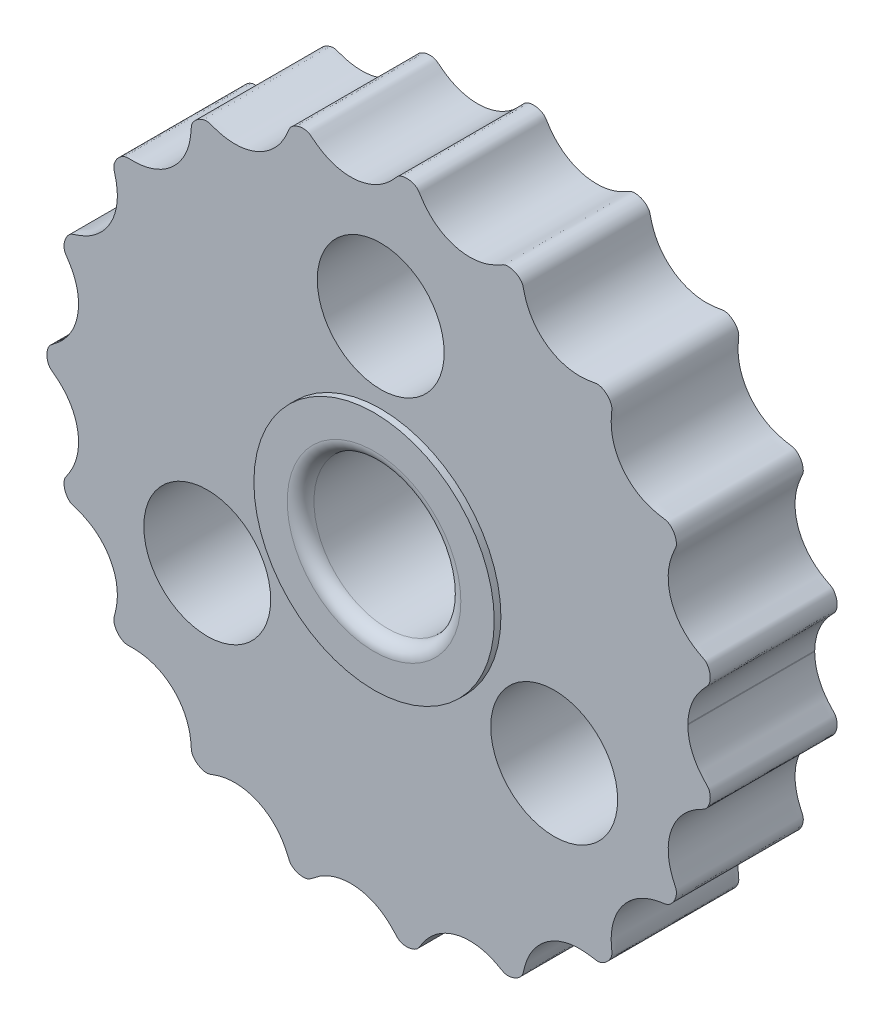
SolidWorks part; units mm, degrees
ref_plane "Ebene vorne" through (0, 0, 0) normal (0, 0, 1) x (1, 0, 0)
ref_plane "Ebene oben" through (0, 0, 0) normal (0, 1, 0) x (1, 0, 0)
ref_plane "Ebene rechts" through (0, 0, 0) normal (1, 0, 0) x (0, 0, -1)
sketch "Skizze1" plane through (0, 0, 0) normal (0, 0, 1) x (1, 0, 0)
  circle A0 centre (0, 0) radius 25
  dimension "D1" = 50
extrude "Aufsatz-Linear austragen1" add sketch "Skizze1" along normal blind 9.5 contours A0
sketch "Skizze3" plane through (0, 0, 9.5) normal (0, 0, 1) x (1, 0, 0)
  circle A0 centre (0, 25) radius 0.5
  circle A1 centre (0, 0) radius 25 construction
extrude "Schnitt-Linear austragen1" cut sketch "Skizze3" against normal up to next contours A0
pattern_circular "Kreismuster3" [suppressed] count 30 over 360 of bodies 102
sketch "Skizze9" plane through (0, 0, 9.5) normal (0, 0, 1) x (1, 0, 0)
  line L0 (23.0004, 0.0609) -> (23, 0)
  spline S0 degree 4 poles (21.8349, 10.4363) (21.7595, 10.2402) (21.6296, 9.8393) (21.51, 9.2154) (21.5169, 8.368) (21.6949, 7.529) (21.9996, 6.8362) (22.3616, 6.2918) (22.7278, 5.8789) (23.0126, 5.6175) (23.2743, 5.4145) (23.4929, 5.2661) (23.6607, 5.1622) (23.8217, 5.0701) (23.9556, 4.9977) (24.0711, 4.9376) (24.1728, 4.8842) (24.259, 4.8347) (24.3648, 4.7517) (24.4596, 4.6337) (24.5411, 4.4963) (24.6203, 4.3033) (24.6742, 4.0826) (24.6893, 3.8352) (24.654, 3.6047) (24.5939, 3.4337) (24.5231, 3.3149) (24.4482, 3.2274) (24.3391, 3.1139) (24.2149, 2.9815) (24.0838, 2.8346) (23.9185, 2.6346) (23.746, 2.4006) (23.5642, 2.1174) (23.3859, 1.7712) (23.2392, 1.419) (23.1381, 1.082) (23.0724, 0.8012) (23.0325, 0.5259) (23.0102, 0.3454) (22.9992, 0.0775) (22.999, -0.0665) (23.009, -0.3222) (23.0286, -0.4951) (23.0652, -0.7605) (23.1283, -1.0483) (23.2566, -1.484) (23.4559, -1.9318) (23.6809, -2.3132) (23.9099, -2.6224) (24.0743, -2.8241) (24.2067, -2.9723) (24.3336, -3.1084) (24.4467, -3.2256) (24.524, -3.3159) (24.583, -3.4156) (24.6246, -3.5208) (24.6638, -3.6686) (24.6852, -3.8609) (24.6735, -4.0869) (24.6205, -4.3068) (24.5464, -4.4848) (24.4695, -4.6144) (24.4037, -4.7024) (24.3311, -4.7784) (24.2516, -4.8395) (24.1377, -4.9039) (24.0001, -4.974) (23.846, -5.0565) (23.6352, -5.1762) (23.3933, -5.3292) (23.1212, -5.5276) (22.8316, -5.7799) (22.5655, -6.0569) (22.2617, -6.4361) (21.9548, -6.9332) (21.7249, -7.4811) (21.5829, -8.0653) (21.5273, -8.5636) (21.5216, -8.9708) (21.5541, -9.3694) (21.6218, -9.7561) (21.7087, -10.0818) (21.7995, -10.3483) (21.8842, -10.5632) (21.9558, -10.729) (22.0248, -10.8829) (22.0924, -11.0248) (22.1404, -11.1746) (22.1504, -11.3468) (22.1274, -11.5442) (22.061, -11.7619) (21.9505, -11.9788) (21.8083, -12.1674) (21.6614, -12.3022) (21.5247, -12.3914) (21.414, -12.4372) (21.3301, -12.4586) (21.2321, -12.4761) (21.1212, -12.4922) (20.9921, -12.5121) (20.8374, -12.539) (20.6763, -12.5709) (20.4655, -12.6198) (20.1205, -12.7175) (19.6539, -12.8972) (19.0899, -13.2109) (18.4957, -13.6939) (17.9798, -14.3033) (17.5818, -15.0184) (17.3599, -15.7125) (17.2758, -16.2728) (17.2579, -16.6757) (17.2603, -16.9123) (17.2683, -17.0871) (17.2802, -17.2498) (17.2921, -17.3816) (17.3037, -17.4944) (17.3123, -17.5952) (17.3148, -17.684) (17.3037, -17.7848) (17.2728, -17.8946) (17.2143, -18.0352) (17.1157, -18.1992) (16.9706, -18.3697) (16.7741, -18.5306) (16.5633, -18.6445) (16.3771, -18.7041) (16.228, -18.7183) (16.1024, -18.7064) (15.9827, -18.6847) (15.837, -18.6581) (15.664, -18.6292) (15.4825, -18.6042) (15.2505, -18.5802) (14.9676, -18.5655) (14.5429, -18.5729) (14.0693, -18.6361) (13.6043, -18.7559) (13.0666, -18.9667) (12.6278, -19.2052) (12.2149, -19.5036) (11.8389, -19.8586) (11.5583, -20.1838) (11.3157, -20.5303) (11.1115, -20.893) (10.9662, -21.2192) (10.865, -21.4994) (10.7941, -21.7329) (10.7511, -21.8937) (10.717, -22.0322) (10.6867, -22.159) (10.6596, -22.2741) (10.6135, -22.4098) (10.5273, -22.5357) (10.4274, -22.6442) (10.2911, -22.7583) (10.1265, -22.8625) (9.947, -22.94) (9.7581, -22.9885) (9.581, -23.009) (9.446, -23.0074) (9.3222, -22.9883) (9.215, -22.9494) (9.1367, -22.9105) (9.0374, -22.8556) (8.9163, -22.7867) (8.7704, -22.7082) (8.5994, -22.6214) (8.2969, -22.4821) (7.9364, -22.3488) (7.5146, -22.2402) (7.0313, -22.1759) (6.6328, -22.1607) (6.2298, -22.1836) (5.826, -22.2463) (5.4253, -22.3496) (5.032, -22.4941) (4.6565, -22.6767) (4.3023, -22.8948) (3.9755, -23.1429) (3.6777, -23.4168) (3.4441, -23.6748) (3.264, -23.904) (3.127, -24.0974) (3.026, -24.2496) (2.9434, -24.3794) (2.8771, -24.486) (2.8107, -24.5788) (2.7442, -24.6523) (2.6543, -24.7214) (2.5172, -24.8007) (2.3431, -24.8698) (2.129, -24.9172) (1.9104, -24.9257) (1.7254, -24.9049) (1.5597, -24.8634) (1.4272, -24.8123) (1.3018, -24.7374) (1.1919, -24.6254) (1.0929, -24.5126) (0.9862, -24.3949) (0.8714, -24.2728) (0.7167, -24.1173) (0.5166, -23.934) (0.1944, -23.6752) (-0.2816, -23.3734) (-0.8873, -23.1037) (-1.633, -22.9219) (-2.4119, -22.88) (-3.1838, -22.9833) (-3.829, -23.1953) (-4.2989, -23.431) (-4.6166, -23.6302) (-4.8236, -23.7746) (-4.9777, -23.8915) (-5.1193, -24.0037) (-5.2422, -24.1039) (-5.3368, -24.1704) (-5.4383, -24.2183) (-5.5428, -24.2496) (-5.6869, -24.2756) (-5.8715, -24.2822) (-6.0864, -24.2562) (-6.2931, -24.1927) (-6.4597, -24.1129) (-6.6006, -24.0204) (-6.7112, -23.9272) (-6.7966, -23.8241) (-6.8508, -23.7158) (-6.8984, -23.6058) (-6.9474, -23.4882) (-7.0086, -23.3469) (-7.0843, -23.183) (-7.1853, -22.982) (-7.3178, -22.7471) (-7.4915, -22.481) (-7.7159, -22.1922) (-7.9683, -21.919) (-8.2484, -21.6651) (-8.561, -21.4293) (-9, -21.1594) (-9.4852, -20.944) (-10.0058, -20.7949) (-10.5401, -20.7187) (-10.9664, -20.7017) (-11.386, -20.7263) (-11.7441, -20.7819) (-12.0407, -20.8508) (-12.2801, -20.9199) (-12.4645, -20.9804) (-12.619, -21.0347) (-12.7443, -21.0813) (-12.8432, -21.1127) (-12.9148, -21.1293) (-13.0155, -21.1409) (-13.1607, -21.1341) (-13.3458, -21.0947) (-13.5626, -21.0052) (-13.7727, -20.87) (-13.9463, -20.7079) (-14.067, -20.5439) (-14.1433, -20.3907) (-14.1772, -20.2506) (-14.1869, -20.1194) (-14.1984, -19.9464) (-14.2135, -19.7574) (-14.2357, -19.56) (-14.2744, -19.3096) (-14.3484, -18.9507) (-14.4988, -18.4602) (-14.7821, -17.8614) (-15.2347, -17.2299) (-15.8123, -16.6797) (-16.4915, -16.2457) (-17.1512, -15.9856) (-17.6884, -15.8653) (-18.0779, -15.8187) (-18.3444, -15.8008) (-18.5515, -15.7964) (-18.7472, -15.7971) (-18.9192, -15.8013) (-19.043, -15.798) (-19.1585, -15.7742) (-19.2639, -15.7342) (-19.3981, -15.6643) (-19.5524, -15.5524) (-19.7098, -15.3942) (-19.8355, -15.2104) (-19.9175, -15.0392) (-19.9694, -14.8748) (-19.9942, -14.7409) (-19.9941, -14.6091) (-19.9622, -14.4594) (-19.9209, -14.3132) (-19.8775, -14.147) (-19.8227, -13.9154) (-19.7703, -13.6388) (-19.7298, -13.3095) (-19.7155, -12.9316) (-19.7343, -12.5536) (-19.7865, -12.1771) (-19.8725, -11.8051) (-20.0235, -11.3478) (-20.2355, -10.9007) (-20.5061, -10.4779) (-20.8313, -10.0898) (-21.1296, -9.7984) (-21.4493, -9.5419) (-21.7859, -9.3207) (-22.0908, -9.1576) (-22.3541, -9.0395) (-22.5745, -8.9534) (-22.7489, -8.8919) (-22.9125, -8.8369) (-23.0664, -8.7897) (-23.2127, -8.7239) (-23.3488, -8.6133) (-23.48, -8.461) (-23.5959, -8.2631) (-23.6806, -8.0335) (-23.7223, -7.802) (-23.7216, -7.6015) (-23.6936, -7.4372) (-23.6459, -7.3113) (-23.587, -7.2131) (-23.5046, -7.0919) (-23.4135, -6.9559) (-23.317, -6.8055) (-23.1954, -6.601) (-23.0687, -6.3633) (-22.9383, -6.0757) (-22.7839, -5.6451) (-22.656, -5.1008) (-22.5992, -4.4221) (-22.6826, -3.6209) (-22.9272, -2.8308) (-23.2818, -2.1836) (-23.6363, -1.7308) (-23.9221, -1.4366) (-24.1011, -1.2722) (-24.239, -1.1546) (-24.372, -1.0482) (-24.4823, -0.963) (-24.578, -0.8915) (-24.662, -0.827) (-24.7323, -0.7672) (-24.8009, -0.6902) (-24.8613, -0.5932) (-24.925, -0.4573) (-24.9789, -0.2784) (-25.008, -0.0615) (-24.998, 0.1569) (-24.9616, 0.3399) (-24.9066, 0.5001) (-24.8504, 0.6156) (-24.7832, 0.7138) (-24.7061, 0.7903) (-24.6412, 0.8433) (-24.5549, 0.909) (-24.4487, 0.9887) (-24.3242, 1.0855) (-24.1833, 1.2011) (-24.0105, 1.3531) (-23.8111, 1.5469) (-23.5946, 1.788) (-23.3715, 2.0829) (-23.1734, 2.3976) (-23.0026, 2.7303) (-22.8251, 3.1685) (-22.6969, 3.6432) (-22.6277, 4.1442) (-22.6242, 4.6617) (-22.6664, 5.0951) (-22.7519, 5.5174) (-22.8777, 5.9244) (-23.0193, 6.2625) (-23.1587, 6.5356) (-23.2844, 6.7524) (-23.3883, 6.9169) (-23.4888, 7.0702) (-23.5875, 7.2108) (-23.6712, 7.3568) (-23.7142, 7.5309) (-23.7261, 7.7309) (-23.6995, 7.9535) (-23.6303, 8.1831) (-23.5263, 8.3908) (-23.4082, 8.549) (-23.2912, 8.6625) (-23.187, 8.7339) (-23.0968, 8.7758) (-22.9816, 8.8159) (-22.8484, 8.8583) (-22.6971, 8.9097) (-22.4871, 8.9859) (-22.2435, 9.0865) (-21.9662, 9.221) (-21.6596, 9.4005) (-21.366, 9.6063) (-21.0151, 9.8992) (-20.6164, 10.3191) (-20.2771, 10.8105) (-20.0144, 11.3636) (-19.8542, 11.8663) (-19.7673, 12.2789) (-19.7222, 12.6923) (-19.7169, 13.1024) (-19.7451, 13.4552) (-19.7902, 13.7494) (-19.8394, 13.9878) (-19.8839, 14.1718) (-19.9244, 14.3263) (-19.9596, 14.452) (-19.9815, 14.5509) (-19.9911, 14.6219) (-19.9935, 14.7217) (-19.9742, 14.8643) (-19.9195, 15.0445) (-19.8125, 15.2522) (-19.6794, 15.4254) (-19.5437, 15.5557) (-19.4017, 15.6607) (-19.2787, 15.7293) (-19.1504, 15.7794) (-19.0246, 15.7985) (-18.927, 15.8005) (-18.8133, 15.7991) (-18.6836, 15.7969) (-18.532, 15.7969) (-18.3106, 15.8023) (-18.0413, 15.8209) (-17.7248, 15.8628) (-17.3647, 15.941) (-16.9178, 16.0786) (-16.3974, 16.3085) (-15.8239, 16.6734) (-15.2485, 17.213) (-14.783, 17.8542) (-14.4878, 18.4827) (-14.3351, 18.9986) (-14.2627, 19.3751) (-14.2269, 19.6306) (-14.2075, 19.8274) (-14.1936, 20.0116) (-14.184, 20.1733) (-14.1697, 20.2905) (-14.1362, 20.4005) (-14.0873, 20.5015) (-14.0059, 20.6294) (-13.8804, 20.7742) (-13.7077, 20.9182) (-13.5127, 21.0276) (-13.335, 21.0939) (-13.1647, 21.1311) (-13.0232, 21.1444) (-12.8817, 21.1276) (-12.7469, 21.0817) (-12.6315, 21.0398) (-12.5001, 20.993) (-12.3519, 20.9431) (-12.1413, 20.8781) (-11.8655, 20.8075) (-11.5389, 20.7468) (-11.1616, 20.7097) (-10.7833, 20.7056) (-10.3038, 20.7432) (-9.7354, 20.8584) (-9.1818, 21.0633) (-8.6608, 21.3563) (-8.2599, 21.6542) (-7.9581, 21.9276) (-7.6875, 22.2243) (-7.4782, 22.5013) (-7.318, 22.7492) (-7.2006, 22.9556) (-7.1162, 23.1178) (-7.0401, 23.2775) (-6.9792, 23.4143) (-6.929, 23.5322) (-6.8829, 23.6417) (-6.8396, 23.7425) (-6.7732, 23.8583) (-6.6528, 23.9827) (-6.4911, 24.0996) (-6.2848, 24.1982) (-6.0489, 24.2635) (-5.8125, 24.2858) (-5.6133, 24.2679) (-5.4554, 24.2266) (-5.3475, 24.1752) (-5.2756, 24.1275) (-5.1963, 24.0667) (-5.1084, 23.9955) (-5.0052, 23.9133) (-4.8796, 23.817) (-4.7458, 23.7196) (-4.5657, 23.5973) (-4.2579, 23.4095) (-3.8065, 23.1883) (-3.1897, 22.9875) (-2.4297, 22.8812) (-1.6328, 22.9188) (-0.8411, 23.1135) (-0.1854, 23.421) (0.2799, 23.7378) (0.5861, 23.9964) (0.7572, 24.1576) (0.8795, 24.2813) (0.9904, 24.3996) (1.0788, 24.4971) (1.1534, 24.5815) (1.2215, 24.6556) (1.2849, 24.7171) (1.366, 24.7765) (1.4665, 24.8274) (1.6073, 24.879) (1.7912, 24.9173) (2.0109, 24.9275) (2.2284, 24.8982) (2.4076, 24.8457) (2.5635, 24.7759) (2.6787, 24.7064) (2.7776, 24.6216) (2.853, 24.522) (2.9089, 24.4353) (2.9741, 24.3312) (3.0513, 24.2111) (3.1673, 24.0378) (3.3314, 23.8136) (3.5412, 23.5623) (3.803, 23.2967) (4.0867, 23.0548) (4.3911, 22.8375) (4.7145, 22.6472) (5.1434, 22.4443) (5.6099, 22.2897) (6.1032, 22.1928) (6.6136, 22.1597) (7.04, 22.1755) (7.456, 22.233) (7.8578, 22.329) (8.1935, 22.443) (8.4659, 22.558) (8.6842, 22.6634) (8.8514, 22.7516) (9.0063, 22.8365) (9.1484, 22.9196) (9.3008, 22.9869) (9.4518, 23.0083) (9.5997, 23.0081) (9.7768, 22.9846) (9.9657, 22.9334) (10.1449, 22.8528) (10.3091, 22.7455) (10.4441, 22.6278) (10.5341, 22.5264) (10.6032, 22.4212) (10.6459, 22.3149) (10.6698, 22.2304) (10.6965, 22.1196) (10.7284, 21.9833) (10.7696, 21.8219) (10.8224, 21.6365) (10.926, 21.3181) (11.074, 20.9612) (11.2824, 20.576) (11.5658, 20.1761) (11.8273, 19.8724) (12.1194, 19.5924) (12.4404, 19.3397) (12.8767, 19.0608) (13.3474, 18.8414) (13.8414, 18.6865) (14.3466, 18.5977) (14.6978, 18.5693) (14.9983, 18.5678) (15.2424, 18.5806) (15.4319, 18.5983) (15.6163, 18.622) (15.7956, 18.651) (15.9629, 18.6804) (16.1188, 18.7114) (16.2634, 18.7186) (16.3919, 18.6957) (16.5434, 18.6484) (16.7128, 18.5663) (16.8932, 18.44) (17.0477, 18.2836) (17.1576, 18.1324) (17.2387, 17.9815) (17.2904, 17.8485) (17.3189, 17.7045) (17.3093, 17.5471) (17.2934, 17.3968) (17.2791, 17.2377) (17.2672, 17.07) (17.2581, 16.8499) (17.2594, 16.5774) (17.2886, 16.1632) (17.3914, 15.6061) (17.6071, 14.9758) (17.9828, 14.3047) (18.4824, 13.7066) (19.0811, 13.2137) (19.6713, 12.887) (20.16, 12.7034) (20.5195, 12.6059) (20.7644, 12.5521) (20.9536, 12.5182) (21.1309, 12.4903) (21.2868, 12.4679) (21.399, 12.4432) (21.5025, 12.4008) (21.5963, 12.345) (21.7134, 12.2561) (21.8437, 12.1238) (21.9702, 11.9469) (22.0634, 11.7504) (22.117, 11.5726) (22.1436, 11.4054) (22.149, 11.2598) (22.129, 11.1267) (22.0845, 11.0132) (22.035, 10.903) (21.9816, 10.7867) (21.919, 10.6454) (21.8499, 10.4782) (21.7706, 10.2666) (21.6878, 10.0086) (21.6103, 9.6986) (21.5509, 9.3355) (21.5224, 8.9626) (21.5272, 8.5827) (21.5787, 8.0866) (21.6972, 7.5846) (21.8865, 7.0905) (22.1457, 6.6199) (22.3909, 6.2662) (22.6666, 5.9438) (22.9679, 5.6541) (23.2503, 5.43) (23.5008, 5.2597) (23.7129, 5.1314) (23.8814, 5.0373) (24.0251, 4.9609) (24.1437, 4.9005) (24.2332, 4.8492) (24.2935, 4.8079) (24.37, 4.7415) (24.4633, 4.6297) (24.5599, 4.466) (24.6407, 4.2447) (24.683, 3.9972) (24.6804, 3.7586) (24.6403, 3.558) (24.5776, 3.3979) (24.4956, 3.2786) (24.4048, 3.1827) (24.2851, 3.0565) (24.1558, 2.9165) (24.0253, 2.7659) (23.8669, 2.5657) (23.6527, 2.2673) (23.442, 1.9019) (23.2546, 1.4742) (23.132, 1.0608) (23.0706, 0.7861) (23.0335, 0.5349) (23.0132, 0.3678) (23.0003, 0.1223) (22.9986, -0.0189) (23.0056, -0.2852) (23.0253, -0.4661) (23.0615, -0.7427) (23.1239, -1.029) (23.2494, -1.4644) (23.4447, -1.9094) (23.6681, -2.2941) (23.8991, -2.6086) (24.0657, -2.8141) (24.1984, -2.9632) (24.3246, -3.0987) (24.4356, -3.2143) (24.5132, -3.3018) (24.5877, -3.4196) (24.6374, -3.5547) (24.6701, -3.7073) (24.6838, -3.9154) (24.6644, -4.1417) (24.6, -4.381) (24.4916, -4.5912) (24.3759, -4.7394) (24.2736, -4.8247) (24.1898, -4.8749) (24.0901, -4.9279) (23.9765, -4.9865) (23.845, -5.0574) (23.6862, -5.1471) (23.5208, -5.2483) (23.3047, -5.3926) (23.0455, -5.59) (22.7627, -5.8442) (22.3976, -6.2458) (22.0314, -6.7792) (21.7172, -7.4627) (21.5252, -8.2962) (21.504, -9.1452) (21.6139, -9.7724) (21.7382, -10.176) (21.8113, -10.3736) knots 0 0 0 0 0 0.004237 0.008483 0.012729 0.016973 0.021413 0.023634 0.025855 0.02808 0.029193 0.030306 0.031182 0.032058 0.032934 0.033372 0.03381 0.034372 0.034934 0.036073 0.036831 0.037589 0.039124 0.04064 0.041779 0.042264 0.042749 0.043421 0.044093 0.045438 0.046411 0.047385 0.049332 0.051278 0.053223 0.055168 0.057112 0.0582 0.059287 0.060374 0.061462 0.062481 0.063501 0.064521 0.06554 0.067576 0.069612 0.073551 0.075471 0.07643 0.07739 0.078785 0.079482 0.08018 0.080676 0.081172 0.081811 0.082451 0.083753 0.085056 0.086348 0.086986 0.087623 0.08809 0.088558 0.089098 0.089639 0.090721 0.091672 0.092623 0.094526 0.09649 0.098454 0.100357 0.102259 0.106274 0.110193 0.112266 0.114339 0.116366 0.118392 0.120318 0.122244 0.123155 0.124065 0.124975 0.125886 0.126558 0.12723 0.128129 0.12933 0.130553 0.131784 0.13302 0.134061 0.134556 0.135052 0.135429 0.135805 0.136559 0.137312 0.138066 0.138968 0.13987 0.141675 0.145292 0.149024 0.152819 0.157032 0.161293 0.165414 0.167417 0.168419 0.16942 0.170182 0.170945 0.171707 0.172088 0.17247 0.172983 0.173496 0.174127 0.174758 0.176047 0.177335 0.178622 0.179842 0.180858 0.181239 0.181621 0.182383 0.183306 0.18423 0.185154 0.186077 0.188008 0.189939 0.193707 0.195683 0.19766 0.201566 0.203743 0.205919 0.208066 0.210213 0.212256 0.214298 0.215257 0.216216 0.217175 0.217654 0.218133 0.218845 0.219557 0.220527 0.221173 0.221818 0.22313 0.224442 0.22509 0.225738 0.226717 0.227156 0.227596 0.228035 0.228475 0.229441 0.230408 0.231375 0.232341 0.236155 0.238143 0.24013 0.242157 0.244184 0.24627 0.248355 0.250487 0.252618 0.254674 0.25673 0.258747 0.260763 0.261683 0.262604 0.263524 0.264444 0.264789 0.265133 0.265821 0.26644 0.267059 0.26832 0.269582 0.270836 0.271447 0.272058 0.273021 0.273691 0.274361 0.275205 0.27605 0.276894 0.277739 0.279628 0.281518 0.285219 0.28907 0.292926 0.296908 0.300855 0.304679 0.306545 0.307478 0.308411 0.309767 0.310445 0.311123 0.311607 0.31209 0.312702 0.313313 0.314555 0.3158 0.31704 0.317653 0.318265 0.319194 0.319946 0.320323 0.320699 0.321608 0.322518 0.323427 0.324337 0.326144 0.327952 0.329828 0.331704 0.333634 0.335564 0.337712 0.342077 0.344294 0.346435 0.348576 0.350665 0.352755 0.353733 0.35471 0.355688 0.356666 0.357036 0.357406 0.357777 0.358147 0.359078 0.360318 0.361577 0.362842 0.364095 0.365072 0.365667 0.366263 0.366989 0.367716 0.369169 0.370082 0.370996 0.372823 0.376553 0.380398 0.384283 0.388402 0.39254 0.396544 0.398494 0.399468 0.400443 0.401928 0.402671 0.403414 0.403914 0.404414 0.405044 0.405674 0.406958 0.408242 0.409517 0.410142 0.410767 0.411715 0.412247 0.41278 0.413844 0.414778 0.415711 0.417578 0.419518 0.421458 0.423328 0.425198 0.427172 0.429146 0.433023 0.435141 0.437259 0.439338 0.441417 0.443393 0.445369 0.446301 0.447232 0.448164 0.449096 0.449784 0.450473 0.451382 0.452594 0.453825 0.455064 0.456299 0.457303 0.457852 0.458401 0.459003 0.459604 0.460806 0.461705 0.462604 0.464401 0.466234 0.468066 0.471816 0.475642 0.479892 0.484207 0.488376 0.490424 0.491448 0.492472 0.493275 0.494078 0.494881 0.495283 0.495684 0.496212 0.496739 0.497357 0.497975 0.499232 0.500491 0.501743 0.502362 0.50298 0.503902 0.504323 0.504745 0.505167 0.505588 0.506507 0.507426 0.508345 0.509264 0.511146 0.513029 0.51487 0.51671 0.518635 0.520559 0.52439 0.526593 0.528795 0.530975 0.533155 0.535264 0.537372 0.538353 0.539334 0.540315 0.541296 0.542048 0.5428 0.543686 0.54487 0.546076 0.547289 0.548505 0.549524 0.55004 0.550557 0.551041 0.551525 0.552494 0.553378 0.554262 0.556029 0.557808 0.559586 0.561418 0.563249 0.567013 0.571226 0.573386 0.575547 0.57763 0.579713 0.581758 0.583803 0.584757 0.585711 0.586665 0.587619 0.587981 0.588342 0.588703 0.589064 0.589991 0.591226 0.592482 0.593745 0.594375 0.595005 0.596035 0.596581 0.597126 0.597563 0.597999 0.598872 0.599744 0.600617 0.602465 0.604312 0.606175 0.608037 0.611883 0.615748 0.619804 0.623847 0.62776 0.629667 0.63062 0.631574 0.63296 0.633653 0.634347 0.63484 0.635333 0.635965 0.636598 0.63789 0.639181 0.640471 0.641084 0.641696 0.642695 0.643315 0.643934 0.644554 0.645174 0.64613 0.647085 0.648997 0.65091 0.652822 0.654719 0.656616 0.660595 0.664476 0.666551 0.668626 0.67065 0.672674 0.674636 0.675617 0.676598 0.67746 0.678322 0.679184 0.679615 0.680046 0.680718 0.68139 0.682294 0.683501 0.68473 0.685967 0.68721 0.688256 0.688745 0.689234 0.689614 0.689994 0.690755 0.691516 0.692276 0.693184 0.694091 0.695906 0.699541 0.703294 0.707104 0.711296 0.715529 0.719623 0.721614 0.722609 0.723605 0.724363 0.72512 0.725878 0.726257 0.726636 0.727147 0.727657 0.728278 0.728898 0.730163 0.731429 0.732687 0.7333 0.733914 0.734868 0.735387 0.735906 0.736425 0.736945 0.737866 0.738787 0.740628 0.742544 0.74446 0.746298 0.748136 0.750076 0.752015 0.75585 0.758014 0.760177 0.762308 0.764439 0.766466 0.768494 0.769446 0.770399 0.771352 0.772304 0.773011 0.773717 0.774692 0.775341 0.77599 0.777308 0.778627 0.779278 0.77993 0.780912 0.781353 0.781795 0.782237 0.782678 0.78365 0.784622 0.785593 0.786565 0.790399 0.792398 0.794396 0.796432 0.798468 0.800544 0.802619 0.806855 0.808898 0.810941 0.812947 0.81395 0.814953 0.815868 0.816783 0.817698 0.818613 0.819297 0.819981 0.820603 0.821225 0.822492 0.82376 0.825019 0.825633 0.826247 0.827208 0.827886 0.828563 0.829411 0.830258 0.831106 0.831953 0.833852 0.83575 0.83947 0.843342 0.847212 0.851172 0.85509 0.858888 0.860742 0.861669 0.862595 0.863943 0.864616 0.86529 0.86577 0.866251 0.866866 0.86748 0.868728 0.86998 0.871226 0.871843 0.872459 0.87339 0.87415 0.87453 0.874909 0.875821 0.876733 0.877645 0.878557 0.880376 0.882194 0.884081 0.885968 0.887906 0.889845 0.894123 0.896327 0.898531 0.900659 0.902786 0.904866 0.906945 0.907918 0.90889 0.909862 0.910835 0.911203 0.911571 0.911939 0.912307 0.913243 0.914489 0.915755 0.917025 0.918283 0.919266 0.919863 0.920461 0.92119 0.921919 0.923377 0.924296 0.925215 0.927054 0.930802 0.932735 0.934668 0.935643 0.936618 0.937593 0.938568 0.939657 0.940745 0.941834 0.942922 0.944896 0.946869 0.950817 0.952789 0.953776 0.954762 0.956135 0.956821 0.957507 0.957996 0.958485 0.959623 0.960381 0.961139 0.962673 0.964189 0.965328 0.965881 0.966433 0.966863 0.967294 0.968154 0.969015 0.969875 0.970969 0.972064 0.974253 0.976438 0.978623 0.98299 0.987244 0.991499 0.995751 1 1 1 1 1 construction
  spline S1 degree 4 poles (23, 0) (23, -0.0443) (23.0016, -0.1335) (23.009, -0.3222) (23.0286, -0.4951) (23.0652, -0.7605) (23.1283, -1.0483) (23.2566, -1.484) (23.4559, -1.9318) (23.6809, -2.3132) (23.9099, -2.6224) (24.0743, -2.8241) (24.2067, -2.9723) (24.3336, -3.1084) (24.4467, -3.2256) (24.524, -3.3159) (24.583, -3.4156) (24.6246, -3.5208) (24.6638, -3.6686) (24.6852, -3.8609) (24.6735, -4.0869) (24.6205, -4.3068) (24.5464, -4.4848) (24.4695, -4.6144) (24.4037, -4.7024) (24.3311, -4.7784) (24.2516, -4.8395) (24.1377, -4.9039) (24.0001, -4.974) (23.846, -5.0565) (23.6352, -5.1762) (23.3933, -5.3292) (23.1212, -5.5276) (22.8316, -5.7799) (22.5655, -6.0569) (22.2617, -6.4361) (21.9548, -6.9332) (21.7249, -7.4811) (21.5829, -8.0653) (21.5273, -8.5636) (21.5216, -8.9708) (21.5541, -9.3694) (21.6218, -9.7561) (21.7087, -10.0818) (21.7995, -10.3483) (21.8842, -10.5632) (21.9558, -10.729) (22.0248, -10.8829) (22.0924, -11.0248) (22.1404, -11.1746) (22.1504, -11.3468) (22.1274, -11.5442) (22.061, -11.7619) (21.9505, -11.9788) (21.8083, -12.1674) (21.6614, -12.3022) (21.5247, -12.3914) (21.414, -12.4372) (21.3301, -12.4586) (21.2321, -12.4761) (21.1212, -12.4922) (20.9921, -12.5121) (20.8374, -12.539) (20.6763, -12.5709) (20.4655, -12.6198) (20.1205, -12.7175) (19.6539, -12.8972) (19.0899, -13.2109) (18.4957, -13.6939) (17.9798, -14.3033) (17.5818, -15.0184) (17.3599, -15.7125) (17.2758, -16.2728) (17.2579, -16.6757) (17.2603, -16.9123) (17.2683, -17.0871) (17.2802, -17.2498) (17.2921, -17.3816) (17.3037, -17.4944) (17.3123, -17.5952) (17.3148, -17.684) (17.3037, -17.7848) (17.2728, -17.8946) (17.2143, -18.0352) (17.1157, -18.1992) (16.9706, -18.3697) (16.7741, -18.5306) (16.5633, -18.6445) (16.3771, -18.7041) (16.228, -18.7183) (16.1024, -18.7064) (15.9827, -18.6847) (15.837, -18.6581) (15.664, -18.6292) (15.4825, -18.6042) (15.2505, -18.5802) (14.9676, -18.5655) (14.5429, -18.5729) (14.0693, -18.6361) (13.6043, -18.7559) (13.0666, -18.9667) (12.6278, -19.2052) (12.2149, -19.5036) (11.8389, -19.8586) (11.5583, -20.1838) (11.3157, -20.5303) (11.1115, -20.893) (10.9662, -21.2192) (10.865, -21.4994) (10.7941, -21.7329) (10.7511, -21.8937) (10.717, -22.0322) (10.6867, -22.159) (10.6596, -22.2741) (10.6135, -22.4098) (10.5273, -22.5357) (10.4274, -22.6442) (10.2911, -22.7583) (10.1265, -22.8625) (9.947, -22.94) (9.7581, -22.9885) (9.581, -23.009) (9.446, -23.0074) (9.3222, -22.9883) (9.215, -22.9494) (9.1367, -22.9105) (9.0374, -22.8556) (8.9163, -22.7867) (8.7704, -22.7082) (8.5994, -22.6214) (8.2969, -22.4821) (7.9364, -22.3488) (7.5146, -22.2402) (7.0313, -22.1759) (6.6328, -22.1607) (6.2298, -22.1836) (5.826, -22.2463) (5.4253, -22.3496) (5.032, -22.4941) (4.6565, -22.6767) (4.3023, -22.8948) (3.9755, -23.1429) (3.6777, -23.4168) (3.4441, -23.6748) (3.264, -23.904) (3.127, -24.0974) (3.026, -24.2496) (2.9434, -24.3794) (2.8771, -24.486) (2.8107, -24.5788) (2.7442, -24.6523) (2.6543, -24.7214) (2.5172, -24.8007) (2.3431, -24.8698) (2.129, -24.9172) (1.9104, -24.9257) (1.7254, -24.9049) (1.5597, -24.8634) (1.4272, -24.8123) (1.3018, -24.7374) (1.1919, -24.6254) (1.0929, -24.5126) (0.9862, -24.3949) (0.8714, -24.2728) (0.7167, -24.1173) (0.5166, -23.934) (0.1944, -23.6752) (-0.2816, -23.3734) (-0.8873, -23.1037) (-1.633, -22.9219) (-2.4119, -22.88) (-3.1838, -22.9833) (-3.829, -23.1953) (-4.2989, -23.431) (-4.6166, -23.6302) (-4.8236, -23.7746) (-4.9777, -23.8915) (-5.1193, -24.0037) (-5.2422, -24.1039) (-5.3368, -24.1704) (-5.4383, -24.2183) (-5.5428, -24.2496) (-5.6869, -24.2756) (-5.8715, -24.2822) (-6.0864, -24.2562) (-6.2931, -24.1927) (-6.4597, -24.1129) (-6.6006, -24.0204) (-6.7112, -23.9272) (-6.7966, -23.8241) (-6.8508, -23.7158) (-6.8984, -23.6058) (-6.9474, -23.4882) (-7.0086, -23.3469) (-7.0843, -23.183) (-7.1853, -22.982) (-7.3178, -22.7471) (-7.4915, -22.481) (-7.7159, -22.1922) (-7.9683, -21.919) (-8.2484, -21.6651) (-8.561, -21.4293) (-9, -21.1594) (-9.4852, -20.944) (-10.0058, -20.7949) (-10.5401, -20.7187) (-10.9664, -20.7017) (-11.386, -20.7263) (-11.7441, -20.7819) (-12.0407, -20.8508) (-12.2801, -20.9199) (-12.4645, -20.9804) (-12.619, -21.0347) (-12.7443, -21.0813) (-12.8432, -21.1127) (-12.9148, -21.1293) (-13.0155, -21.1409) (-13.1607, -21.1341) (-13.3458, -21.0947) (-13.5626, -21.0052) (-13.7727, -20.87) (-13.9463, -20.7079) (-14.067, -20.5439) (-14.1433, -20.3907) (-14.1772, -20.2506) (-14.1869, -20.1194) (-14.1984, -19.9464) (-14.2135, -19.7574) (-14.2357, -19.56) (-14.2744, -19.3096) (-14.3484, -18.9507) (-14.4988, -18.4602) (-14.7821, -17.8614) (-15.2347, -17.2299) (-15.8123, -16.6797) (-16.4915, -16.2457) (-17.1512, -15.9856) (-17.6884, -15.8653) (-18.0779, -15.8187) (-18.3444, -15.8008) (-18.5515, -15.7964) (-18.7472, -15.7971) (-18.9192, -15.8013) (-19.043, -15.798) (-19.1585, -15.7742) (-19.2639, -15.7342) (-19.3981, -15.6643) (-19.5524, -15.5524) (-19.7098, -15.3942) (-19.8355, -15.2104) (-19.9175, -15.0392) (-19.9694, -14.8748) (-19.9942, -14.7409) (-19.9941, -14.6091) (-19.9622, -14.4594) (-19.9209, -14.3132) (-19.8775, -14.147) (-19.8227, -13.9154) (-19.7703, -13.6388) (-19.7298, -13.3095) (-19.7155, -12.9316) (-19.7343, -12.5536) (-19.7865, -12.1771) (-19.8725, -11.8051) (-20.0235, -11.3478) (-20.2355, -10.9007) (-20.5061, -10.4779) (-20.8313, -10.0898) (-21.1296, -9.7984) (-21.4493, -9.5419) (-21.7859, -9.3207) (-22.0908, -9.1576) (-22.3541, -9.0395) (-22.5745, -8.9534) (-22.7489, -8.8919) (-22.9125, -8.8369) (-23.0664, -8.7897) (-23.2127, -8.7239) (-23.3488, -8.6133) (-23.48, -8.461) (-23.5959, -8.2631) (-23.6806, -8.0335) (-23.7223, -7.802) (-23.7216, -7.6015) (-23.6936, -7.4372) (-23.6459, -7.3113) (-23.587, -7.2131) (-23.5046, -7.0919) (-23.4135, -6.9559) (-23.317, -6.8055) (-23.1954, -6.601) (-23.0687, -6.3633) (-22.9383, -6.0757) (-22.7839, -5.6451) (-22.656, -5.1008) (-22.5992, -4.4221) (-22.6826, -3.6209) (-22.9272, -2.8308) (-23.2818, -2.1836) (-23.6363, -1.7308) (-23.9221, -1.4366) (-24.1011, -1.2722) (-24.239, -1.1546) (-24.372, -1.0482) (-24.4823, -0.963) (-24.578, -0.8915) (-24.662, -0.827) (-24.7323, -0.7672) (-24.8009, -0.6902) (-24.8613, -0.5932) (-24.925, -0.4573) (-24.9789, -0.2784) (-25.008, -0.0615) (-24.998, 0.1569) (-24.9616, 0.3399) (-24.9066, 0.5001) (-24.8504, 0.6156) (-24.7832, 0.7138) (-24.7061, 0.7903) (-24.6412, 0.8433) (-24.5549, 0.909) (-24.4487, 0.9887) (-24.3242, 1.0855) (-24.1833, 1.2011) (-24.0105, 1.3531) (-23.8111, 1.5469) (-23.5946, 1.788) (-23.3715, 2.0829) (-23.1734, 2.3976) (-23.0026, 2.7303) (-22.8251, 3.1685) (-22.6969, 3.6432) (-22.6277, 4.1442) (-22.6242, 4.6617) (-22.6664, 5.0951) (-22.7519, 5.5174) (-22.8777, 5.9244) (-23.0193, 6.2625) (-23.1587, 6.5356) (-23.2844, 6.7524) (-23.3883, 6.9169) (-23.4888, 7.0702) (-23.5875, 7.2108) (-23.6712, 7.3568) (-23.7142, 7.5309) (-23.7261, 7.7309) (-23.6995, 7.9535) (-23.6303, 8.1831) (-23.5263, 8.3908) (-23.4082, 8.549) (-23.2912, 8.6625) (-23.187, 8.7339) (-23.0968, 8.7758) (-22.9816, 8.8159) (-22.8484, 8.8583) (-22.6971, 8.9097) (-22.4871, 8.9859) (-22.2435, 9.0865) (-21.9662, 9.221) (-21.6596, 9.4005) (-21.366, 9.6063) (-21.0151, 9.8992) (-20.6164, 10.3191) (-20.2771, 10.8105) (-20.0144, 11.3636) (-19.8542, 11.8663) (-19.7673, 12.2789) (-19.7222, 12.6923) (-19.7169, 13.1024) (-19.7451, 13.4552) (-19.7902, 13.7494) (-19.8394, 13.9878) (-19.8839, 14.1718) (-19.9244, 14.3263) (-19.9596, 14.452) (-19.9815, 14.5509) (-19.9911, 14.6219) (-19.9935, 14.7217) (-19.9742, 14.8643) (-19.9195, 15.0445) (-19.8125, 15.2522) (-19.6794, 15.4254) (-19.5437, 15.5557) (-19.4017, 15.6607) (-19.2787, 15.7293) (-19.1504, 15.7794) (-19.0246, 15.7985) (-18.927, 15.8005) (-18.8133, 15.7991) (-18.6836, 15.7969) (-18.532, 15.7969) (-18.3106, 15.8023) (-18.0413, 15.8209) (-17.7248, 15.8628) (-17.3647, 15.941) (-16.9178, 16.0786) (-16.3974, 16.3085) (-15.8239, 16.6734) (-15.2485, 17.213) (-14.783, 17.8542) (-14.4878, 18.4827) (-14.3351, 18.9986) (-14.2627, 19.3751) (-14.2269, 19.6306) (-14.2075, 19.8274) (-14.1936, 20.0116) (-14.184, 20.1733) (-14.1697, 20.2905) (-14.1362, 20.4005) (-14.0873, 20.5015) (-14.0059, 20.6294) (-13.8804, 20.7742) (-13.7077, 20.9182) (-13.5127, 21.0276) (-13.335, 21.0939) (-13.1647, 21.1311) (-13.0232, 21.1444) (-12.8817, 21.1276) (-12.7469, 21.0817) (-12.6315, 21.0398) (-12.5001, 20.993) (-12.3519, 20.9431) (-12.1413, 20.8781) (-11.8655, 20.8075) (-11.5389, 20.7468) (-11.1616, 20.7097) (-10.7833, 20.7056) (-10.3038, 20.7432) (-9.7354, 20.8584) (-9.1818, 21.0633) (-8.6608, 21.3563) (-8.2599, 21.6542) (-7.9581, 21.9276) (-7.6875, 22.2243) (-7.4782, 22.5013) (-7.318, 22.7492) (-7.2006, 22.9556) (-7.1162, 23.1178) (-7.0401, 23.2775) (-6.9792, 23.4143) (-6.929, 23.5322) (-6.8829, 23.6417) (-6.8396, 23.7425) (-6.7732, 23.8583) (-6.6528, 23.9827) (-6.4911, 24.0996) (-6.2848, 24.1982) (-6.0489, 24.2635) (-5.8125, 24.2858) (-5.6133, 24.2679) (-5.4554, 24.2266) (-5.3475, 24.1752) (-5.2756, 24.1275) (-5.1963, 24.0667) (-5.1084, 23.9955) (-5.0052, 23.9133) (-4.8796, 23.817) (-4.7458, 23.7196) (-4.5657, 23.5973) (-4.2579, 23.4095) (-3.8065, 23.1883) (-3.1897, 22.9875) (-2.4297, 22.8812) (-1.6328, 22.9188) (-0.8411, 23.1135) (-0.1854, 23.421) (0.2799, 23.7378) (0.5861, 23.9964) (0.7572, 24.1576) (0.8795, 24.2813) (0.9904, 24.3996) (1.0788, 24.4971) (1.1534, 24.5815) (1.2215, 24.6556) (1.2849, 24.7171) (1.366, 24.7765) (1.4665, 24.8274) (1.6073, 24.879) (1.7912, 24.9173) (2.0109, 24.9275) (2.2284, 24.8982) (2.4076, 24.8457) (2.5635, 24.7759) (2.6787, 24.7064) (2.7776, 24.6216) (2.853, 24.522) (2.9089, 24.4353) (2.9741, 24.3312) (3.0513, 24.2111) (3.1673, 24.0378) (3.3314, 23.8136) (3.5412, 23.5623) (3.803, 23.2967) (4.0867, 23.0548) (4.3911, 22.8375) (4.7145, 22.6472) (5.1434, 22.4443) (5.6099, 22.2897) (6.1032, 22.1928) (6.6136, 22.1597) (7.04, 22.1755) (7.456, 22.233) (7.8578, 22.329) (8.1935, 22.443) (8.4659, 22.558) (8.6842, 22.6634) (8.8514, 22.7516) (9.0063, 22.8365) (9.1484, 22.9196) (9.3008, 22.9869) (9.4518, 23.0083) (9.5997, 23.0081) (9.7768, 22.9846) (9.9657, 22.9334) (10.1449, 22.8528) (10.3091, 22.7455) (10.4441, 22.6278) (10.5341, 22.5264) (10.6032, 22.4212) (10.6459, 22.3149) (10.6698, 22.2304) (10.6965, 22.1196) (10.7284, 21.9833) (10.7696, 21.8219) (10.8224, 21.6365) (10.926, 21.3181) (11.074, 20.9612) (11.2824, 20.576) (11.5658, 20.1761) (11.8273, 19.8724) (12.1194, 19.5924) (12.4404, 19.3397) (12.8767, 19.0608) (13.3474, 18.8414) (13.8414, 18.6865) (14.3466, 18.5977) (14.6978, 18.5693) (14.9983, 18.5678) (15.2424, 18.5806) (15.4319, 18.5983) (15.6163, 18.622) (15.7956, 18.651) (15.9629, 18.6804) (16.1188, 18.7114) (16.2634, 18.7186) (16.3919, 18.6957) (16.5434, 18.6484) (16.7128, 18.5663) (16.8932, 18.44) (17.0477, 18.2836) (17.1576, 18.1324) (17.2387, 17.9815) (17.2904, 17.8485) (17.3189, 17.7045) (17.3093, 17.5471) (17.2934, 17.3968) (17.2791, 17.2377) (17.2672, 17.07) (17.2581, 16.8499) (17.2594, 16.5774) (17.2886, 16.1632) (17.3914, 15.6061) (17.6071, 14.9758) (17.9828, 14.3047) (18.4824, 13.7066) (19.0811, 13.2137) (19.6713, 12.887) (20.16, 12.7034) (20.5195, 12.6059) (20.7644, 12.5521) (20.9536, 12.5182) (21.1309, 12.4903) (21.2868, 12.4679) (21.399, 12.4432) (21.5025, 12.4008) (21.5963, 12.345) (21.7134, 12.2561) (21.8437, 12.1238) (21.9702, 11.9469) (22.0634, 11.7504) (22.117, 11.5726) (22.1436, 11.4054) (22.149, 11.2598) (22.129, 11.1267) (22.0845, 11.0132) (22.035, 10.903) (21.9816, 10.7867) (21.919, 10.6454) (21.8499, 10.4782) (21.7706, 10.2666) (21.6878, 10.0086) (21.6103, 9.6986) (21.5509, 9.3355) (21.5224, 8.9626) (21.5272, 8.5827) (21.5787, 8.0866) (21.6972, 7.5846) (21.8865, 7.0905) (22.1457, 6.6199) (22.3909, 6.2662) (22.6666, 5.9438) (22.9679, 5.6541) (23.2503, 5.43) (23.5008, 5.2597) (23.7129, 5.1314) (23.8814, 5.0373) (24.0251, 4.9609) (24.1437, 4.9005) (24.2332, 4.8492) (24.2935, 4.8079) (24.37, 4.7415) (24.4633, 4.6297) (24.5599, 4.466) (24.6407, 4.2447) (24.683, 3.9972) (24.6804, 3.7586) (24.6403, 3.558) (24.5776, 3.3979) (24.4956, 3.2786) (24.4048, 3.1827) (24.2851, 3.0565) (24.1558, 2.9165) (24.0253, 2.7659) (23.8669, 2.5657) (23.6527, 2.2673) (23.442, 1.9019) (23.2546, 1.4742) (23.132, 1.0608) (23.0706, 0.7861) (23.0335, 0.5349) (23.0132, 0.3678) (23.0038, 0.1889) (23.0011, 0.1033) (23.0004, 0.0609) knots 0.061462 0.061462 0.061462 0.061462 0.061462 0.062481 0.063501 0.064521 0.06554 0.067576 0.069612 0.073551 0.075471 0.07643 0.07739 0.078785 0.079482 0.08018 0.080676 0.081172 0.081811 0.082451 0.083753 0.085056 0.086348 0.086986 0.087623 0.08809 0.088558 0.089098 0.089639 0.090721 0.091672 0.092623 0.094526 0.09649 0.098454 0.100357 0.102259 0.106274 0.110193 0.112266 0.114339 0.116366 0.118392 0.120318 0.122244 0.123155 0.124065 0.124975 0.125886 0.126558 0.12723 0.128129 0.12933 0.130553 0.131784 0.13302 0.134061 0.134556 0.135052 0.135429 0.135805 0.136559 0.137312 0.138066 0.138968 0.13987 0.141675 0.145292 0.149024 0.152819 0.157032 0.161293 0.165414 0.167417 0.168419 0.16942 0.170182 0.170945 0.171707 0.172088 0.17247 0.172983 0.173496 0.174127 0.174758 0.176047 0.177335 0.178622 0.179842 0.180858 0.181239 0.181621 0.182383 0.183306 0.18423 0.185154 0.186077 0.188008 0.189939 0.193707 0.195683 0.19766 0.201566 0.203743 0.205919 0.208066 0.210213 0.212256 0.214298 0.215257 0.216216 0.217175 0.217654 0.218133 0.218845 0.219557 0.220527 0.221173 0.221818 0.22313 0.224442 0.22509 0.225738 0.226717 0.227156 0.227596 0.228035 0.228475 0.229441 0.230408 0.231375 0.232341 0.236155 0.238143 0.24013 0.242157 0.244184 0.24627 0.248355 0.250487 0.252618 0.254674 0.25673 0.258747 0.260763 0.261683 0.262604 0.263524 0.264444 0.264789 0.265133 0.265821 0.26644 0.267059 0.26832 0.269582 0.270836 0.271447 0.272058 0.273021 0.273691 0.274361 0.275205 0.27605 0.276894 0.277739 0.279628 0.281518 0.285219 0.28907 0.292926 0.296908 0.300855 0.304679 0.306545 0.307478 0.308411 0.309767 0.310445 0.311123 0.311607 0.31209 0.312702 0.313313 0.314555 0.3158 0.31704 0.317653 0.318265 0.319194 0.319946 0.320323 0.320699 0.321608 0.322518 0.323427 0.324337 0.326144 0.327952 0.329828 0.331704 0.333634 0.335564 0.337712 0.342077 0.344294 0.346435 0.348576 0.350665 0.352755 0.353733 0.35471 0.355688 0.356666 0.357036 0.357406 0.357777 0.358147 0.359078 0.360318 0.361577 0.362842 0.364095 0.365072 0.365667 0.366263 0.366989 0.367716 0.369169 0.370082 0.370996 0.372823 0.376553 0.380398 0.384283 0.388402 0.39254 0.396544 0.398494 0.399468 0.400443 0.401928 0.402671 0.403414 0.403914 0.404414 0.405044 0.405674 0.406958 0.408242 0.409517 0.410142 0.410767 0.411715 0.412247 0.41278 0.413844 0.414778 0.415711 0.417578 0.419518 0.421458 0.423328 0.425198 0.427172 0.429146 0.433023 0.435141 0.437259 0.439338 0.441417 0.443393 0.445369 0.446301 0.447232 0.448164 0.449096 0.449784 0.450473 0.451382 0.452594 0.453825 0.455064 0.456299 0.457303 0.457852 0.458401 0.459003 0.459604 0.460806 0.461705 0.462604 0.464401 0.466234 0.468066 0.471816 0.475642 0.479892 0.484207 0.488376 0.490424 0.491448 0.492472 0.493275 0.494078 0.494881 0.495283 0.495684 0.496212 0.496739 0.497357 0.497975 0.499232 0.500491 0.501743 0.502362 0.50298 0.503902 0.504323 0.504745 0.505167 0.505588 0.506507 0.507426 0.508345 0.509264 0.511146 0.513029 0.51487 0.51671 0.518635 0.520559 0.52439 0.526593 0.528795 0.530975 0.533155 0.535264 0.537372 0.538353 0.539334 0.540315 0.541296 0.542048 0.5428 0.543686 0.54487 0.546076 0.547289 0.548505 0.549524 0.55004 0.550557 0.551041 0.551525 0.552494 0.553378 0.554262 0.556029 0.557808 0.559586 0.561418 0.563249 0.567013 0.571226 0.573386 0.575547 0.57763 0.579713 0.581758 0.583803 0.584757 0.585711 0.586665 0.587619 0.587981 0.588342 0.588703 0.589064 0.589991 0.591226 0.592482 0.593745 0.594375 0.595005 0.596035 0.596581 0.597126 0.597563 0.597999 0.598872 0.599744 0.600617 0.602465 0.604312 0.606175 0.608037 0.611883 0.615748 0.619804 0.623847 0.62776 0.629667 0.63062 0.631574 0.63296 0.633653 0.634347 0.63484 0.635333 0.635965 0.636598 0.63789 0.639181 0.640471 0.641084 0.641696 0.642695 0.643315 0.643934 0.644554 0.645174 0.64613 0.647085 0.648997 0.65091 0.652822 0.654719 0.656616 0.660595 0.664476 0.666551 0.668626 0.67065 0.672674 0.674636 0.675617 0.676598 0.67746 0.678322 0.679184 0.679615 0.680046 0.680718 0.68139 0.682294 0.683501 0.68473 0.685967 0.68721 0.688256 0.688745 0.689234 0.689614 0.689994 0.690755 0.691516 0.692276 0.693184 0.694091 0.695906 0.699541 0.703294 0.707104 0.711296 0.715529 0.719623 0.721614 0.722609 0.723605 0.724363 0.72512 0.725878 0.726257 0.726636 0.727147 0.727657 0.728278 0.728898 0.730163 0.731429 0.732687 0.7333 0.733914 0.734868 0.735387 0.735906 0.736425 0.736945 0.737866 0.738787 0.740628 0.742544 0.74446 0.746298 0.748136 0.750076 0.752015 0.75585 0.758014 0.760177 0.762308 0.764439 0.766466 0.768494 0.769446 0.770399 0.771352 0.772304 0.773011 0.773717 0.774692 0.775341 0.77599 0.777308 0.778627 0.779278 0.77993 0.780912 0.781353 0.781795 0.782237 0.782678 0.78365 0.784622 0.785593 0.786565 0.790399 0.792398 0.794396 0.796432 0.798468 0.800544 0.802619 0.806855 0.808898 0.810941 0.812947 0.81395 0.814953 0.815868 0.816783 0.817698 0.818613 0.819297 0.819981 0.820603 0.821225 0.822492 0.82376 0.825019 0.825633 0.826247 0.827208 0.827886 0.828563 0.829411 0.830258 0.831106 0.831953 0.833852 0.83575 0.83947 0.843342 0.847212 0.851172 0.85509 0.858888 0.860742 0.861669 0.862595 0.863943 0.864616 0.86529 0.86577 0.866251 0.866866 0.86748 0.868728 0.86998 0.871226 0.871843 0.872459 0.87339 0.87415 0.87453 0.874909 0.875821 0.876733 0.877645 0.878557 0.880376 0.882194 0.884081 0.885968 0.887906 0.889845 0.894123 0.896327 0.898531 0.900659 0.902786 0.904866 0.906945 0.907918 0.90889 0.909862 0.910835 0.911203 0.911571 0.911939 0.912307 0.913243 0.914489 0.915755 0.917025 0.918283 0.919266 0.919863 0.920461 0.92119 0.921919 0.923377 0.924296 0.925215 0.927054 0.930802 0.932735 0.934668 0.935643 0.936618 0.937593 0.938568 0.938568 0.938568 0.938568 0.938568
extrude "Schnitt-Linear austragen6" cut sketch "Skizze9" against normal blind 9.5 flip side to cut
sketch "Skizze23" plane through (0, 0, 9.5) normal (0, 0, 1) x (1, 0, 0)
  circle A0 centre (0, 0) radius 9
extrude "Aufsatz-Linear austragen2" add sketch "Skizze23" along normal blind 0.5
sketch "Skizze21" plane through (0, 0, 0) normal (0, 0, -1) x (-1, 0, 0)
  circle A0 centre (0, 0) radius 5.5
  dimension "D1" = 11
extrude "Schnitt-Linear austragen11" cut sketch "Skizze21" against normal blind 10
sketch "Skizze22" plane through (0, 0, 0) normal (0, 0, -1) x (-1, 0, 0)
  circle A0 centre (0, 0) radius 15
  circle A1 centre (0, 15) radius 4.75
  circle A2 centre (12.9904, -7.5) radius 4.75
  circle A3 centre (-12.9904, -7.5) radius 4.75
  point P12 (0, 0)
  dimension "D1" = 3
  dimension "D2" = 9.5
fillet "Verrundung1" radius 1 2 edges at (-5.5, 0, 0) (-5.5, 0, 10)
extrude "Schnitt-Linear austragen12" cut sketch "Skizze22" against normal blind 10 contours A1 | A2 | A3
